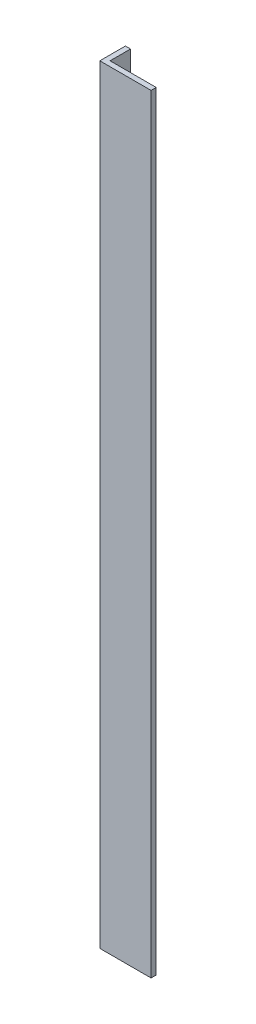
SolidWorks part; units mm, degrees
ref_plane "Front Plane" through (0, 0, 0) normal (0, 0, 1) x (1, 0, 0)
ref_plane "Top Plane" through (0, 0, 0) normal (0, 1, 0) x (1, 0, 0)
ref_plane "Right Plane" through (0, 0, 0) normal (1, 0, 0) x (0, 0, -1)
sketch "Sketch1" plane through (0, 0, 0) normal (0, 1, 0) x (1, 0, 0)
  line L0 (0, 0) -> (0, 10)
  line L1 (0, 10) -> (2, 10)
  line L2 (2, 10) -> (2, 2)
  line L3 (2, 2) -> (20, 2)
  line L4 (20, 2) -> (20, 0)
  line L5 (20, 0) -> (0, 0)
extrude "Boss-Extrude1" add sketch "Sketch1" along normal blind 300
hole_wizard "Ø3.0mm Dowel Hole1" positions "Sketch3" profile "Sketch5" hole size "Ø3.0" standard "ISO" end condition up to next
sketch "Sketch3" plane through (0, 0, 0) normal (-1, 0, 0) x (0, 0, 1)
  point P0 (-7.25, 2.75)
  point P3 (-7.25, 2.75)
sketch "Sketch5" plane through (0, 2.75, -7.25) normal (0, 1, 0) x (0, 0, 1)
  line L0 (0, 0) -> (0, 2)
  line L1 (0, 2) -> (1.5, 2)
  line L2 (1.5, 2) -> (1.5, 0)
  line L5 (1.5, 0) -> (0, 0)
  line L11 (0, -6.35) -> (0, 107.95) construction
  dimension "Thru Hole Dia." = 3
  dimension "Thru Hole Depth" = 2
hole_wizard "Ø3.0mm Dowel Hole2" positions "Sketch6" profile "Sketch7" hole size "Ø3.0" standard "ISO" end condition up to next
sketch "Sketch6" plane through (0, 0, 0) normal (-1, 0, 0) x (0, 0, 1)
  point P0 (-7.25, 211.25)
sketch "Sketch7" plane through (0, 211.25, -7.25) normal (0, 1, 0) x (0, 0, 1)
  line L0 (0, 0) -> (0, 2)
  line L1 (0, 2) -> (1.5, 2)
  line L2 (1.5, 2) -> (1.5, 0)
  line L5 (1.5, 0) -> (0, 0)
  line L11 (0, -6.35) -> (0, 107.95) construction
  dimension "Thru Hole Dia." = 3
  dimension "Thru Hole Depth" = 2
hole_wizard "Ø3.0 (3) Diameter Hole1" positions "Sketch8" profile "Sketch9" hole size "Ø3.0" standard "ISO" end condition through all
sketch "Sketch8" plane through (2, 325.4076, 141.138) normal (1, 0, 0) x (0, 0, 1)
  point P0 (-147.138, 37.4076)
  point P1 (-147.138, 61.4076)
sketch "Sketch9" plane through (2, 288, -6) normal (0, 1, 0) x (0, 0, -1)
  line L0 (0, 0) -> (0, 2)
  line L1 (0, 2) -> (1.5, 2)
  line L2 (1.5, 2) -> (1.5, 0)
  line L3 (1.5, 0) -> (0, 0)
  line L4 (0, -6.35) -> (0, 107.95) construction
  dimension "Thru Hole Dia." = 3
  dimension "Thru Hole Depth" = 2
